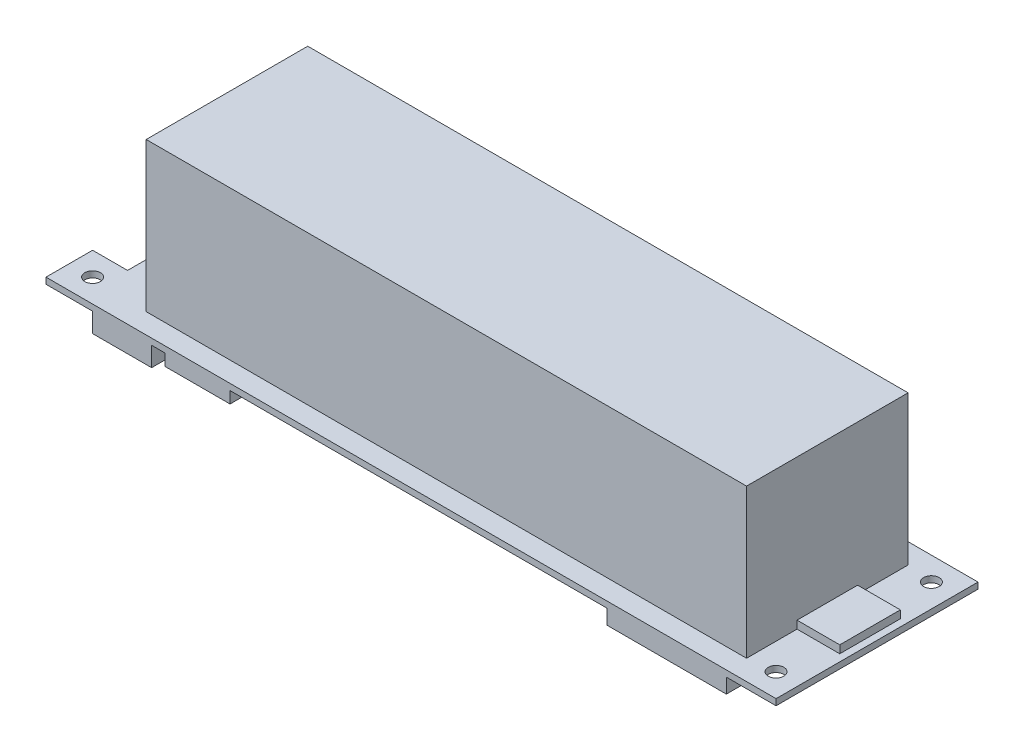
SolidWorks part; units mm, degrees
ref_plane "前视基准面" through (0, 0, 0) normal (0, 0, 1) x (1, 0, 0)
ref_plane "上视基准面" through (0, 0, 0) normal (0, 1, 0) x (1, 0, 0)
ref_plane "右视基准面" through (0, 0, 0) normal (1, 0, 0) x (0, 0, -1)
other "Configuration Table"
sketch "草图1" plane through (0, 0, 0) normal (0, 1, 0) x (1, 0, 0)
  line L1 (-47, -13) -> (47, -13)
  line L2 (-47, -13) -> (-47, 13)
  line L3 (-47, 13) -> (47, 13)
  line L4 (47, -13) -> (47, 13)
  line L5 (-47, -13) -> (47, 13) construction
  line L6 (-47, 13) -> (47, -13) construction
  circle A0 centre (-44, 10) radius 1
  circle A1 centre (-44, -10) radius 1
  circle A2 centre (44, 10) radius 1
  circle A3 centre (44, -10) radius 1
  point P0 (0, 0)
  dimension "D3" = 2
  dimension "D4" = 3
  dimension "D1" = 94
  dimension "D2" = 26
  dimension "D5" = 3
  dimension "D6" = 3
  dimension "D7" = 3
extrude "凸台-拉伸1" add sketch "草图1" along normal blind 0.8
sketch "草图2" plane through (0, 0.8, 0) normal (0, 1, 0) x (1, 0, 0)
  line L0 (-47, 13) -> (-47, -13) construction
  line L1 (-42.2, 3.9) -> (-36.7, 3.9)
  line L2 (-42.2, 3.9) -> (-42.2, -3.9)
  line L3 (-42.2, -3.9) -> (-36.7, -3.9)
  line L4 (-36.7, 3.9) -> (-36.7, -3.9)
  line L5 (40.6, 3.9) -> (46.1, 3.9)
  line L6 (40.6, 3.9) -> (40.6, -3.9)
  line L7 (40.6, -3.9) -> (46.1, -3.9)
  line L8 (46.1, 3.9) -> (46.1, -3.9)
  line L9 (47, -13) -> (47, 13) construction
  line L10 (-36.7, 0) -> (0, 0) construction
  line L11 (47, 13) -> (-47, 13) construction
  line L13 (-36.7, 10.4) -> (40.6, 10.4)
  line L14 (-36.7, 10.4) -> (-36.7, -10.4)
  line L15 (-36.7, -10.4) -> (40.6, -10.4)
  line L16 (40.6, 10.4) -> (40.6, -10.4)
  dimension "D1" = 4.8
  dimension "D2" = 0.9
  dimension "D3" = 10.3
  dimension "D4" = 9.1
  dimension "D5" = 2.6
extrude "凸台-拉伸2" add sketch "草图2" along normal blind 1 contours L3 L4 L1 L2 | L7 L8 L5 L6
extrude "凸台-拉伸3" add sketch "草图2<3>" along normal blind 19.2 contours L15 L16 L13 L14
sketch "草图2<3>" plane through (0, 0.8, 0) normal (0, 1, 0) x (1, 0, 0) same geometry as "草图2"
sketch "草图3" plane through (0, 0, 0) normal (0, -1, 0) x (1, 0, 0)
  line L0 (-47, 13) -> (47, 13) construction
  line L1 (25.2, 13) -> (40.6, 13)
  line L2 (25.2, 13) -> (25.2, -2.1)
  line L3 (25.2, -2.1) -> (40.6, -2.1)
  line L4 (40.6, 13) -> (40.6, -2.1)
  line L5 (-47, -13) -> (-47, 13) construction
  line L6 (-30.7, 3.1) -> (-24, 3.1)
  line L7 (-30.7, 3.1) -> (-30.7, -3.1)
  line L8 (-30.7, -3.1) -> (-24, -3.1)
  line L9 (-24, 3.1) -> (-24, -3.1)
  line L10 (-19.425, 3.1) -> (-12.725, 3.1)
  line L11 (-19.425, 3.1) -> (-19.425, -3.1)
  line L12 (-19.425, -3.1) -> (-12.725, -3.1)
  line L13 (-12.725, 3.1) -> (-12.725, -3.1)
  line L14 (-8.15, 3.1) -> (-1.45, 3.1)
  line L15 (-8.15, 3.1) -> (-8.15, -3.1)
  line L16 (-8.15, -3.1) -> (-1.45, -3.1)
  line L17 (-1.45, 3.1) -> (-1.45, -3.1)
  line L18 (3.125, 3.1) -> (9.825, 3.1)
  line L19 (3.125, 3.1) -> (3.125, -3.1)
  line L20 (3.125, -3.1) -> (9.825, -3.1)
  line L21 (9.825, 3.1) -> (9.825, -3.1)
  line L22 (14.4, 3.1) -> (21.1, 3.1)
  line L23 (14.4, 3.1) -> (14.4, -3.1)
  line L24 (14.4, -3.1) -> (21.1, -3.1)
  line L25 (21.1, 3.1) -> (21.1, -3.1)
  line L26 (-41, 13) -> (-33.4, 13)
  line L27 (-41, 13) -> (-41, 7.1)
  line L28 (-41, 7.1) -> (-33.4, 7.1)
  line L29 (-33.4, 13) -> (-33.4, 7.1)
  line L30 (-31.7, 13) -> (-23.3, 13)
  line L31 (-31.7, 13) -> (-31.7, 7.1)
  line L32 (-31.7, 7.1) -> (-23.3, 7.1)
  line L33 (-23.3, 13) -> (-23.3, 7.1)
  line L34 (-47, 7) -> (-42.5, 7)
  line L35 (-47, 7) -> (-47, -1.7)
  line L36 (-47, -1.7) -> (-42.5, -1.7)
  line L37 (-42.5, 7) -> (-42.5, -1.7)
  line L38 (47, 13) -> (47, -13) construction
  line L39 (47, -13) -> (-47, -13) construction
  line L40 (9.825, 0) -> (14.4, 0) construction
  line L41 (-1.45, 0) -> (3.125, 0) construction
  line L42 (-12.725, 0) -> (-8.15, 0) construction
  line L43 (-24, 0) -> (-19.425, 0) construction
  line M4 (47, 13) -> (-47, 13)
  dimension "D1" = 72.2
  dimension "D2" = 6.4
  dimension "D3" = 10.9
  dimension "D4" = 25.9
  dimension "D5" = 16.3
  dimension "D6" = 9.9
  dimension "D7" = 61.4
  dimension "D8" = 15.3
  dimension "D9" = 70.3
  dimension "D10" = 20.1
  dimension "D11" = 20.1
  dimension "D12" = 6
  dimension "D13" = 80.4
  dimension "D14" = 6
  dimension "D15" = 11.3
  dimension "D16" = 4.5
extrude "凸台-拉伸4" add sketch "草图3" along normal blind 1.9 contours L3 L4 L1 L2
extrude "凸台-拉伸5" add sketch "草图3<3>" along normal blind 1 contours L8 L9 L6 L7 | L12 L13 L10 L11 | L16 L17 L14 L15 | L20 L21 L18 L19 | L24 L25 L22 L23
sketch "草图3<3>" plane through (0, 0, 0) normal (0, -1, 0) x (1, 0, 0) same geometry as "草图3"
extrude "凸台-拉伸6" add sketch "草图3<4>" along normal blind 1.5 contours L32 L33 L30 L31
sketch "草图3<4>" plane through (0, 0, 0) normal (0, -1, 0) x (1, 0, 0) same geometry as "草图3"
extrude "凸台-拉伸7" add sketch "草图3<5>" along normal blind 2.5 contours L29 L27 L28 M4 region at (-37.2, 0, 10.05)
sketch "草图3<5>" plane through (0, 0, 0) normal (0, -1, 0) x (1, 0, 0) same geometry as "草图3"
extrude "切除-拉伸1" cut sketch "草图3<6>" against normal through all contours L36 L37 L34 L35
sketch "草图3<6>" plane through (0, 0, 0) normal (0, -1, 0) x (1, 0, 0) same geometry as "草图3"
